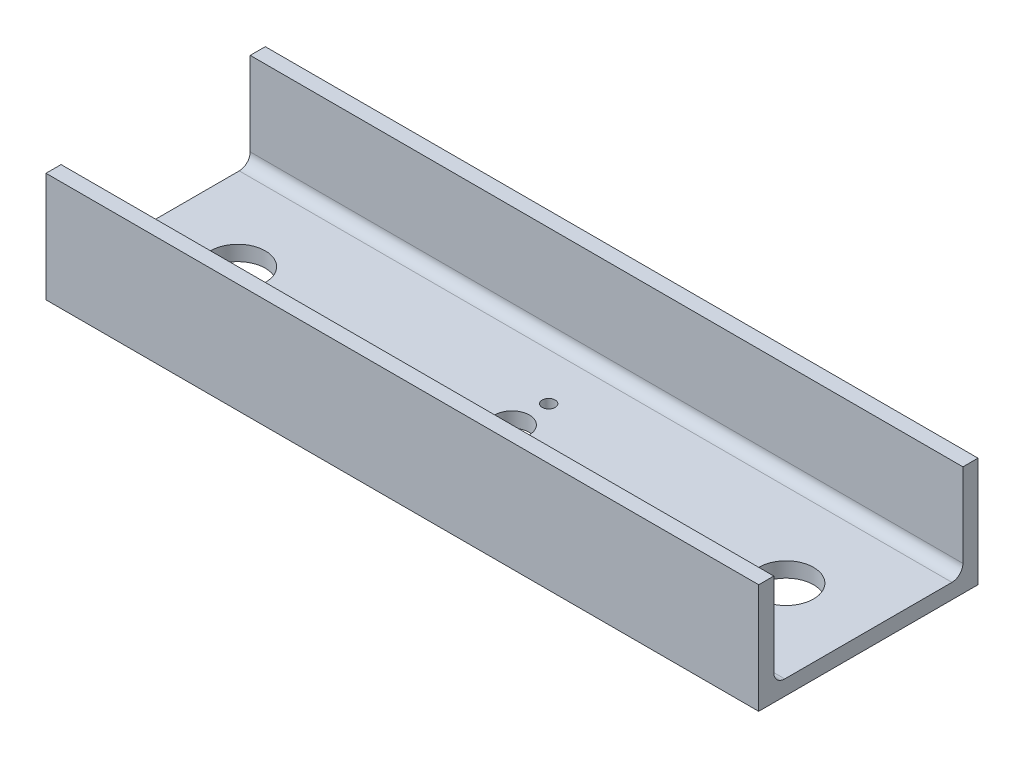
SolidWorks part; units mm, degrees
ref_plane "Front Plane" through (0, 0, 0) normal (0, 0, 1) x (1, 0, 0)
ref_plane "Top Plane" through (0, 0, 0) normal (0, 1, 0) x (1, 0, 0)
ref_plane "Right Plane" through (0, 0, 0) normal (1, 0, 0) x (0, 0, -1)
sketch "Sketch1" plane through (0, 0, 0) normal (1, 0, 0) x (0, 0, -1)
  line L0 (-21.9075, 9.2075) -> (21.9075, 9.2075)
  line L1 (-25.4, -12.7) -> (25.4, -12.7)
  line L2 (-25.4, -12.7) -> (-25.4, 12.7)
  line L3 (-25.4, 12.7) -> (25.4, 12.7)
  line L4 (25.4, -12.7) -> (25.4, 12.7)
  line L5 (-25.4, -12.7) -> (25.4, 12.7) construction
  line L6 (-25.4, 12.7) -> (25.4, -12.7) construction
  line L7 (21.9075, -6.6675) -> (21.9075, 9.2075)
  line L8 (-19.3675, -9.2075) -> (19.3675, -9.2075)
  line L9 (-21.9075, -6.6675) -> (-21.9075, 9.2075)
  line L10 (-21.9075, 9.2075) -> (-21.9075, 12.7)
  line L11 (21.9075, 9.2075) -> (21.9075, 12.7)
  line L12 (21.9075, -9.2075) -> (21.9075, 9.2075) construction
  line L13 (-21.9075, -9.2075) -> (21.9075, -9.2075) construction
  line L14 (-21.9075, -9.2075) -> (-21.9075, 9.2075) construction
  arc A0 (21.9075, -6.6675) -> (19.3675, -9.2075) centre (19.3675, -6.6675) cw
  arc A1 (-19.3675, -9.2075) -> (-21.9075, -6.6675) centre (-19.3675, -6.6675) cw
  point P0 (0, 0)
  dimension "D4" = 2.54
  dimension "D1" = 25.4
  dimension "D2" = 50.8
  dimension "D3" = 3.4925
extrude "Boss-Extrude1" add sketch "Sketch1" along normal blind 165.1 contours L8 A1 L9 L10 L3 L2 L1 L4 L11 L7 A0 region at (0, 1.27, 22.4755)
sketch "Sketch2" plane through (0, -12.7, 0) normal (0, -1, 0) x (1, 0, 0)
  line L0 (0, 0) -> (165.1, 0) construction
  line L3 (0, 25.4) -> (0, -25.4) construction
  line L4 (165.1, 25.4) -> (165.1, -25.4) construction
  line L11 (0, 0) -> (19.05, 0)
  line L12 (165.1, 0) -> (146.05, 0)
  line L13 (82.55, 8.5) -> (82.55, -8.5) construction
  circle A4 centre (19.05, 0) radius 6.35
  circle A5 centre (146.05, 0) radius 6.35
  circle A6 centre (82.55, 8.5) radius 1.5
  circle A7 centre (82.55, -8.5) radius 1.5
  circle A8 centre (82.55, 0) radius 4
  point P14 (82.55, 0)
  point P15 (82.55, 0)
  dimension "D5" = 17
  dimension "D2" = 12.7
  dimension "D4" = 12.7
  dimension "D6" = 3
  dimension "D7" = 3
  dimension "D8" = 8
  dimension "D1" = 19.05
  dimension "D3" = 19.05
extrude "Cut-Extrude1" cut sketch "Sketch2" against normal blind 11.938 contours A4 | A6 | A8 | A7 | A5 region at (19.05, -12.7, -6.1704) region at (139.8796, -12.7, 0) region at (82.55, -12.7, 8.5) region at (82.55, -12.7, -8.5) region at (82.55, -12.7, 0)
sketch "Sketch3" plane through (0, -12.7, 0) normal (0, -1, 0) x (1, 0, 0)
  line L0 (19.05, 0) -> (41.0012, 0)
  line L1 (41.0012, 0) -> (60.5988, 0)
  circle A0 centre (19.05, 0) radius 21.9512
  circle A1 centre (82.55, 0) radius 21.9512
  circle A2 centre (146.05, 0) radius 21.9512
